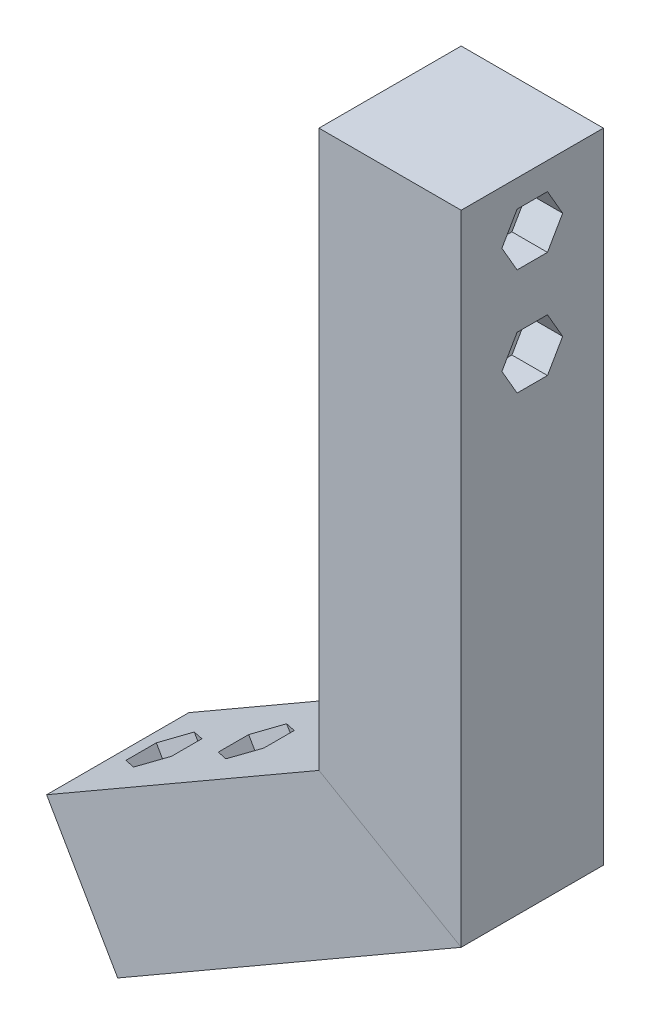
SolidWorks part; units mm, degrees
note: The reader was unsure of these and kept them because the rebuilt part matched: shared geometry of "Sketch5<3>", "Sketch6<5>".
ref_plane "Front Plane" through (0, 0, 0) normal (0, 0, 1) x (1, 0, 0)
ref_plane "Top Plane" through (0, 0, 0) normal (0, 1, 0) x (1, 0, 0)
ref_plane "Right Plane" through (0, 0, 0) normal (1, 0, 0) x (0, 0, -1)
sketch "Sketch1" plane through (0, 0, 0) normal (0, 0, 1) x (1, 0, 0)
  line L0 (0, 0) -> (43.3013, 25)
  line L1 (43.3013, 25) -> (43.3013, 109)
  dimension "D1" = 30
  dimension "D2" = 50
  dimension "D3" = 84
ref_plane "Plane1" through (0, 0, 0) normal (-0.866, -0.5, 0) x (0, 0, 1)
sketch "Sketch4" plane through (0, 0, 0) normal (-0.866, -0.5, 0) x (0, 0, 1)
  line L1 (-10, -10) -> (10, -10)
  line L2 (-10, -10) -> (-10, 10)
  line L3 (-10, 10) -> (10, 10)
  line L4 (10, -10) -> (10, 10)
  line L5 (-10, -10) -> (10, 10) construction
  line L6 (-10, 10) -> (10, -10) construction
  point P0 (0, 0)
  dimension "D1" = 20
  dimension "D2" = 20
sweep "Sweep1" add profiles "Sketch4" path "Sketch1"
sketch "Sketch5" plane through (-5, 8.6603, 0) normal (-0.5, 0.866, 0) x (0.866, 0.5, 0)
  line L0 (0, 0) -> (44.2265, 0) construction
  line L1 (44.2265, 10) -> (44.2265, -10) construction
  line L2 (0, -10) -> (0, 10) construction
  line L3 (7.5, 4.2724) -> (3.8, 2.1362)
  line L4 (3.8, 2.1362) -> (3.8, -2.1362)
  line L5 (3.8, -2.1362) -> (7.5, -4.2724)
  line L6 (7.5, -4.2724) -> (11.2, -2.1362)
  line L7 (11.2, -2.1362) -> (11.2, 2.1362)
  line L8 (11.2, 2.1362) -> (7.5, 4.2724)
  line L9 (22.5, 4.2724) -> (18.8, 2.1362)
  line L10 (18.8, 2.1362) -> (18.8, -2.1362)
  line L11 (18.8, -2.1362) -> (22.5, -4.2724)
  line L12 (22.5, -4.2724) -> (26.2, -2.1362)
  line L13 (26.2, -2.1362) -> (26.2, 2.1362)
  line L14 (26.2, 2.1362) -> (22.5, 4.2724)
  circle A0 centre (7.5, 0) radius 3.7 construction
  circle A1 centre (22.5, 0) radius 3.7 construction
  circle A2 centre (7.5, 0) radius 2
  circle A3 centre (22.5, 0) radius 2
  dimension "D4" = 4
  dimension "D1" = 7.5
  dimension "D2" = 15
  dimension "D3" = 7.4
extrude "Cut-Extrude1" cut sketch "Sketch5" against normal up to next contours A2 | A3
extrude "Cut-Extrude2" cut sketch "Sketch5<3>" against normal blind 5 contours L7 L8 L3 L4 L5 L6 A2 | L13 L14 L9 L10 L11 L12 A3
sketch "Sketch5<3>" plane through (-5, 8.6603, 0) normal (-0.5, 0.866, 0) x (0.866, 0.5, 0) same geometry as "Sketch5"
sketch "Sketch6" plane through (53.3013, 0, -53.3013) normal (-1, 0, 0) x (0, 0, 1)
  line L0 (53.3013, 109) -> (53.3013, 19.2265) construction
  line L1 (63.3013, 19.2265) -> (43.3013, 19.2265) construction
  line L2 (43.3013, 109) -> (63.3013, 109) construction
  line L3 (57.5737, 101.5) -> (55.4375, 105.2)
  line L4 (55.4375, 105.2) -> (51.1651, 105.2)
  line L5 (51.1651, 105.2) -> (49.0289, 101.5)
  line L6 (49.0289, 101.5) -> (51.1651, 97.8)
  line L7 (51.1651, 97.8) -> (55.4375, 97.8)
  line L8 (55.4375, 97.8) -> (57.5737, 101.5)
  line L9 (57.5737, 86.5) -> (55.4375, 90.2)
  line L10 (55.4375, 90.2) -> (51.1651, 90.2)
  line L11 (51.1651, 90.2) -> (49.0289, 86.5)
  line L12 (49.0289, 86.5) -> (51.1651, 82.8)
  line L13 (51.1651, 82.8) -> (55.4375, 82.8)
  line L14 (55.4375, 82.8) -> (57.5737, 86.5)
  circle A0 centre (53.3013, 101.5) radius 3.7 construction
  circle A1 centre (53.3013, 86.5) radius 3.7 construction
  circle A2 centre (53.3013, 101.5) radius 2
  circle A3 centre (53.3013, 86.5) radius 2
  point P2 (53.3013, 19.2265)
  point P3 (0, 0)
  point P22 (5.5879, 19.2265)
  point P25 (53.3013, 109)
  dimension "D4" = 4
  dimension "D1" = 7.5
  dimension "D2" = 15
  dimension "D3" = 7.4
extrude "Cut-Extrude3" cut sketch "Sketch6" along normal through all contours A2 | A3
extrude "Cut-Extrude4" cut sketch "Sketch6<5>" along normal blind 5 contours L8 L7 L6 L5 L4 L3 A2 | L14 L13 L12 L11 L10 L9 A3
sketch "Sketch6<5>" plane through (53.3013, 0, -53.3013) normal (-1, 0, 0) x (0, 0, 1) same geometry as "Sketch6"
